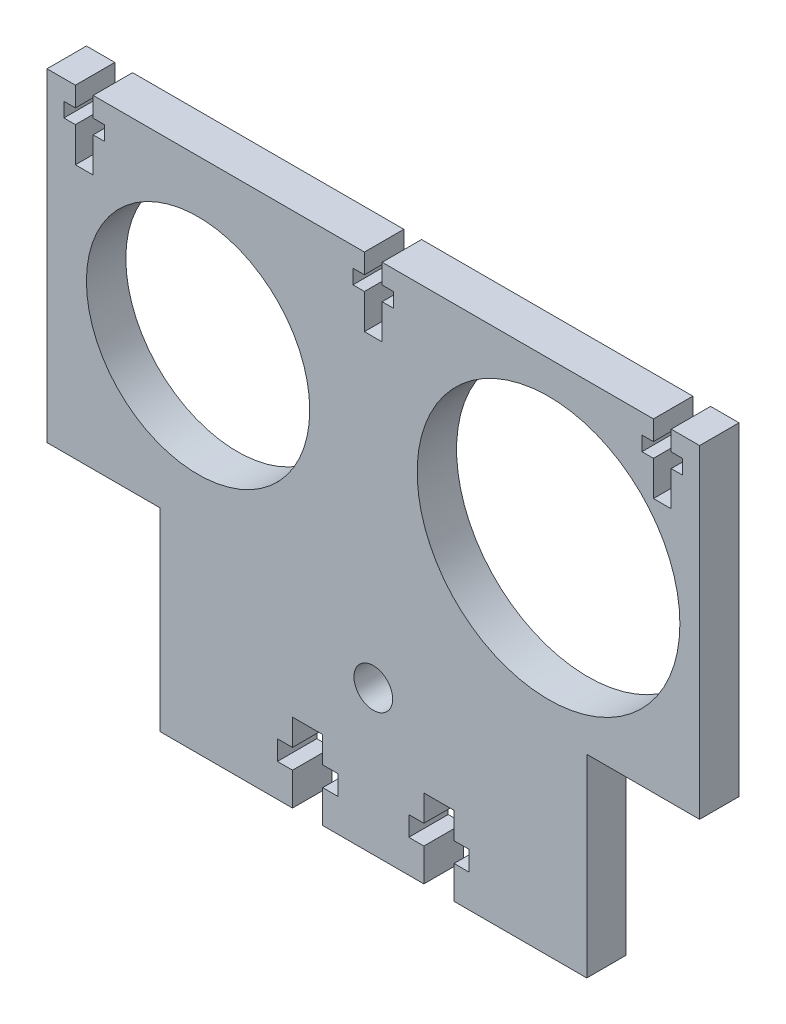
SolidWorks part; units mm, degrees
material "ABS"
ref_plane "Front Plane" through (0, 0, 0) normal (0, 0, 1) x (1, 0, 0)
ref_plane "Top Plane" through (0, 0, 0) normal (0, 1, 0) x (1, 0, 0)
ref_plane "Right Plane" through (0, 0, 0) normal (1, 0, 0) x (0, 0, -1)
sketch "Sketch1" plane through (0, 0, 0) normal (0, 0, 1) x (1, 0, 0)
  line L0 (0, 0) -> (-26.6757, 31.7908) construction
  line L1 (0, 0) -> (0, 56.7908) construction
  line L2 (-32.5, 7.5) -> (-32.5, -22)
  line L3 (-32.5, -22) -> (32.5, -22)
  line L4 (32.5, 7.5) -> (49.6757, 7.5)
  line L5 (0, 0) -> (0, -22) construction
  line L6 (49.6757, 7.5) -> (49.6757, 56.7908)
  line L7 (0, 0) -> (26.6757, 31.7908) construction
  line L10 (-32.5, 7.5) -> (-49.6757, 7.5)
  line L11 (-49.6757, 7.5) -> (-49.6757, 56.7908)
  line L12 (-49.6757, 56.7908) -> (49.6757, 56.7908)
  line L13 (32.5, 7.5) -> (32.5, -22)
  circle A0 centre (0, 0) radius 2.95
  circle A1 centre (-26.6757, 31.7908) radius 17
  circle A2 centre (26.6757, 31.7908) radius 20
  point P16 (0, 56.7908)
  dimension "D1" = 5.9
  dimension "D9" = 34
  dimension "D10" = 40
  dimension "D2" = 41.5
  dimension "D4" = 40
  dimension "D5" = 22
  dimension "D6" = 65
  dimension "D7" = 29.5
  dimension "D8" = 23
  dimension "D3" = 25
  dimension "D11" = 40
extrude "Boss-Extrude1" add sketch "Sketch1" along normal blind 6
sketch "Sketch3" plane through (0, 0, 6) normal (0, 0, 1) x (1, 0, 0)
  line L0 (-32.5, -22) -> (32.5, -22) construction
  line L1 (-12.3, -22) -> (-7.7, -22)
  line L2 (-12.3, -22) -> (-12.3, -17)
  line L3 (-12.3, -10) -> (-7.7, -10)
  line L4 (-7.7, -22) -> (-7.7, -17)
  line L5 (0, 0) -> (0, -22) construction
  line L6 (-7.7, -14) -> (-5.4, -14)
  line L7 (-14.6, -14) -> (-12.3, -14)
  line L8 (-14.6, -14) -> (-14.6, -17)
  line L9 (-14.6, -17) -> (-12.3, -17)
  line L10 (-5.4, -14) -> (-5.4, -17)
  line L11 (-12.3, -14) -> (-12.3, -10)
  line L12 (-7.7, -17) -> (-5.4, -17)
  line L13 (-7.7, -14) -> (-7.7, -10)
  line L14 (7.7, -14) -> (7.7, -10)
  line L15 (7.7, -17) -> (5.4, -17)
  line L16 (12.3, -14) -> (12.3, -10)
  line L17 (5.4, -14) -> (5.4, -17)
  line L18 (14.6, -17) -> (12.3, -17)
  line L19 (14.6, -14) -> (14.6, -17)
  line L20 (14.6, -14) -> (12.3, -14)
  line L21 (7.7, -14) -> (5.4, -14)
  line L22 (7.7, -22) -> (7.7, -17)
  line L23 (12.3, -10) -> (7.7, -10)
  line L24 (12.3, -22) -> (12.3, -17)
  line L25 (12.3, -22) -> (7.7, -22)
  point P6 (-10, -10)
  point P18 (-13.45, -17)
  dimension "D1" = 4.6
  dimension "D2" = 10
  dimension "D3" = 12
  dimension "D4" = 9.2
  dimension "D5" = 3
  dimension "D6" = 5
extrude "Cut-Extrude2" cut sketch "Sketch3" against normal through all
sketch "Sketch4" plane through (0, 0, 6) normal (0, 0, 1) x (1, 0, 0)
  line L0 (42.65, 56.7908) -> (42.65, 53.7908)
  line L1 (49.6757, 56.7908) -> (-49.6757, 56.7908) construction
  line L2 (42.65, 53.7908) -> (40.9, 53.7908)
  line L3 (40.9, 53.7908) -> (40.9, 51.5908)
  line L4 (40.9, 51.5908) -> (42.65, 51.5908)
  line L5 (42.65, 51.5908) -> (42.65, 46.2908)
  line L6 (42.65, 46.2908) -> (45.35, 46.2908)
  line L7 (45.35, 46.2908) -> (45.35, 51.5908)
  line L8 (45.35, 51.5908) -> (47.1, 51.5908)
  line L9 (47.1, 51.5908) -> (47.1, 53.7908)
  line L10 (47.1, 53.7908) -> (45.35, 53.7908)
  line L11 (45.35, 53.7908) -> (45.35, 56.7908)
  line L12 (45.35, 56.7908) -> (42.65, 56.7908)
  line L13 (0, 0) -> (0, 56.7908) construction
  line L14 (-45.35, 56.7908) -> (-42.65, 56.7908)
  line L15 (-45.35, 53.7908) -> (-45.35, 56.7908)
  line L16 (-47.1, 53.7908) -> (-45.35, 53.7908)
  line L17 (-47.1, 51.5908) -> (-47.1, 53.7908)
  line L18 (-45.35, 51.5908) -> (-47.1, 51.5908)
  line L19 (-45.35, 46.2908) -> (-45.35, 51.5908)
  line L20 (-42.65, 46.2908) -> (-45.35, 46.2908)
  line L21 (-42.65, 51.5908) -> (-42.65, 46.2908)
  line L22 (-40.9, 51.5908) -> (-42.65, 51.5908)
  line L23 (-40.9, 53.7908) -> (-40.9, 51.5908)
  line L24 (-42.65, 53.7908) -> (-40.9, 53.7908)
  line L25 (-42.65, 56.7908) -> (-42.65, 53.7908)
  line L26 (-1.35, 56.7908) -> (1.35, 56.7908)
  line L27 (1.35, 56.7908) -> (1.35, 53.7908)
  line L28 (1.35, 53.7908) -> (3.1, 53.7908)
  line L29 (3.1, 53.7908) -> (3.1, 51.5908)
  line L30 (3.1, 51.5908) -> (1.35, 51.5908)
  line L31 (1.35, 51.5908) -> (1.35, 46.2908)
  line L32 (1.35, 46.2908) -> (-1.35, 46.2908)
  line L33 (-1.35, 46.2908) -> (-1.35, 51.5908)
  line L34 (-1.35, 51.5908) -> (-3.1, 51.5908)
  line L35 (-3.1, 51.5908) -> (-3.1, 53.7908)
  line L36 (-3.1, 53.7908) -> (-1.35, 53.7908)
  line L37 (-1.35, 53.7908) -> (-1.35, 56.7908)
  point P18 (44, 46.2908)
  point P46 (0, 46.2908)
  dimension "D1" = 2.7
  dimension "D2" = 2.2
  dimension "D3" = 6.2
  dimension "D4" = 3
  dimension "D5" = 10.5
  dimension "D6" = 44
extrude "Cut-Extrude3" cut sketch "Sketch4" against normal through all
equation "\"smallPulleyTeeth\"= 15"
equation "\"largePulleyTeeth\"= 30"
equation "\"eighthThick\"= 3.0mm"
equation "\"sixteenthThick\"= 1.7mm"
equation "\"quarterThick\"=6.0mm"
equation "\"OD\"= 145mm"
equation "\"puckAngle\"= 60.5deg"
equation "\"puckDiam\"= 76.5mm"
equation "\"axlePress\"= 5.9mm"
equation "\"D1@Sketch1\"=\"axlePress\""
equation "\"D1@Boss-Extrude1\"=\"quarterThick\""
equation "\"press\"= 0.2mm"
equation "\"wheelClear\"= 0.3mm"
equation "\"10-32clear\"= 4.8mm"
equation "\"D1@Sketch3\"=\"10-32clear\" - \"press\""
equation "\"6-32clear\"= 3.3mm"
equation "\"8-32clear\"= 4.0mm"
equation "\"wheelHeight\"= 22mm"
equation "\"D5@Sketch1\"=\"wheelHeight\""
equation "\"4-40clear\"= 3.0mm"
equation "\"wheelWell\"= 65mm"
equation "\"D6@Sketch1\"=\"wheelWell\""
equation "\"D7@Sketch1\"=\"eighthThick\"*10 - 0.5"
equation "\"puckDist\"= 85mm"
equation "\"scoopFillet\"= 5mm"
equation "\"10-32tap\"= 4.45mm"
equation "\"ledSmall\"= 3.1mm"
equation "\"ledLarge\"= 4.2mm"
equation "\"ledLength\"= 4.2mm"
equation "\"4-40close\"= 2.7mm"
equation "\"4-40nutThick\"= 2.2mm"
equation "\"4-40nutWidth\"= 6.2mm"
equation "\"D3@Sketch4\"=\"4-40nutWidth\""
equation "\"D2@Sketch4\"=\"4-40nutThick\""
equation "\"D1@Sketch4\"=\"4-40close\""
